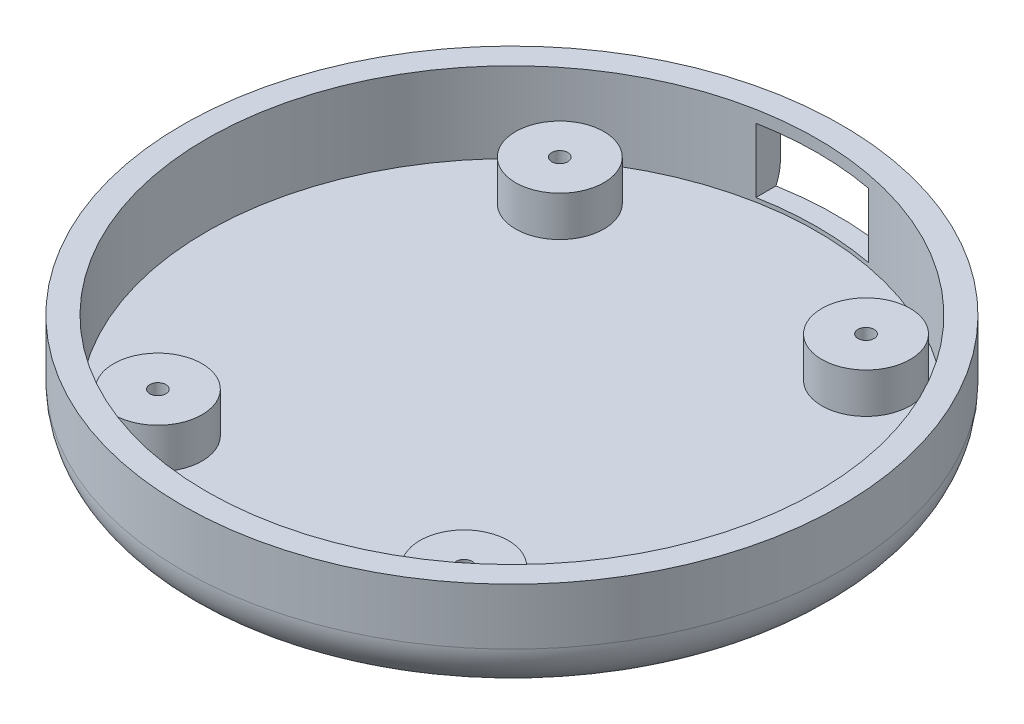
SolidWorks part; units mm, degrees
ref_plane "Front Plane" through (0, 0, 0) normal (0, 0, 1) x (1, 0, 0)
ref_plane "Top Plane" through (0, 0, 0) normal (0, 1, 0) x (1, 0, 0)
ref_plane "Right Plane" through (0, 0, 0) normal (1, 0, 0) x (0, 0, -1)
sketch "Sketch1" plane through (0, 0, 0) normal (0, 1, 0) x (1, 0, 0)
  circle A0 centre (0, 0) radius 41
  circle A1 centre (-19.05, 25) radius 2.5
  circle A2 centre (19.05, 25) radius 2.5
  circle A3 centre (19.05, -25) radius 2.5
  circle A4 centre (-19.05, -25) radius 2.5
  dimension "D1" = 82
  dimension "D2" = 5
  dimension "D5" = 25
  dimension "D6" = 19.05
  dimension "D3" = 2
  dimension "D4" = 2
extrude "Boss-Extrude1" add sketch "Sketch1" along normal blind 3
sketch "Sketch3" plane through (0, 3, 0) normal (0, 1, 0) x (1, 0, 0)
  circle A0 centre (0, 0) radius 41
  circle A1 centre (0, 0) radius 38
  circle A2 centre (-19.05, 25) radius 2.5
  circle A3 centre (-19.05, 25) radius 5.5
  circle A4 centre (19.05, 25) radius 2.5
  circle A5 centre (19.05, 25) radius 5.5
  circle A6 centre (19.05, -25) radius 2.5
  circle A7 centre (19.05, -25) radius 5.5
  circle A8 centre (-19.05, -25) radius 2.5
  circle A9 centre (-19.05, -25) radius 5.5
  circle M2 centre (19.05, -25) radius 2.5
  circle M3 centre (-19.05, 25) radius 2.5
  circle M4 centre (0, 0) radius 41
  circle M5 centre (19.05, 25) radius 2.5
  circle M6 centre (-19.05, -25) radius 2.5
  dimension "D1" = 76
  dimension "D2" = 5
  dimension "D3" = 11
  dimension "D4" = 2
  dimension "D5" = 2
extrude "Boss-Extrude2" add sketch "Sketch3" along normal blind 10 contours A1 M4 region at (-39.8403, 3, 0)
extrude "Boss-Extrude3" add sketch "Sketch3<3>" along normal blind 3 contours A3 M3 | A5 M5 | A9 M6 | A7 M2 region at (-24.3944, 3, -25) region at (13.7056, 3, -25) region at (13.7056, 3, 25) region at (-24.3944, 3, 25)
sketch "Sketch3<3>" plane through (0, 3, 0) normal (0, 1, 0) x (1, 0, 0) same geometry as "Sketch3"
sketch "Sketch4" plane through (0, 6, 0) normal (0, 1, 0) x (1, 0, 0)
  circle A0 centre (-19.05, 25) radius 5.5
  circle A1 centre (-19.05, 25) radius 1
  circle A2 centre (19.05, 25) radius 5.5
  circle A3 centre (19.05, 25) radius 1
  circle A4 centre (19.05, -25) radius 5.5
  circle A5 centre (19.05, -25) radius 1
  circle A6 centre (-19.05, -25) radius 5.5
  circle A7 centre (-19.05, -25) radius 1
  dimension "D1" = 2
  dimension "D2" = 11
  dimension "D3" = 2
  dimension "D4" = 2
extrude "Boss-Extrude4" add sketch "Sketch4" along normal blind 2
fillet "Fillet1" radius 6 1 edges at (0, 0, 41)
sketch "Sketch6" plane through (0, 0, 0) normal (0, 0, 1) x (1, 0, 0)
  line L0 (0, -7.15) -> (0, 7.15) construction
  line L1 (-7, 11.5) -> (7, 11.5)
  line L2 (-7, 11.5) -> (-7, 3.5)
  line L3 (-7, 3.5) -> (7, 3.5)
  line L4 (7, 11.5) -> (7, 3.5)
  line L5 (-7, 11.5) -> (7, 3.5) construction
  line L6 (-7, 3.5) -> (7, 11.5) construction
  line L7 (45.1, 0) -> (-45.1, 0) construction
  point P0 (0, 7.5)
  dimension "D1" = 14
  dimension "D2" = 8
  dimension "D3" = 3.5
extrude "Cut-Extrude1" cut sketch "Sketch6" against normal through all
